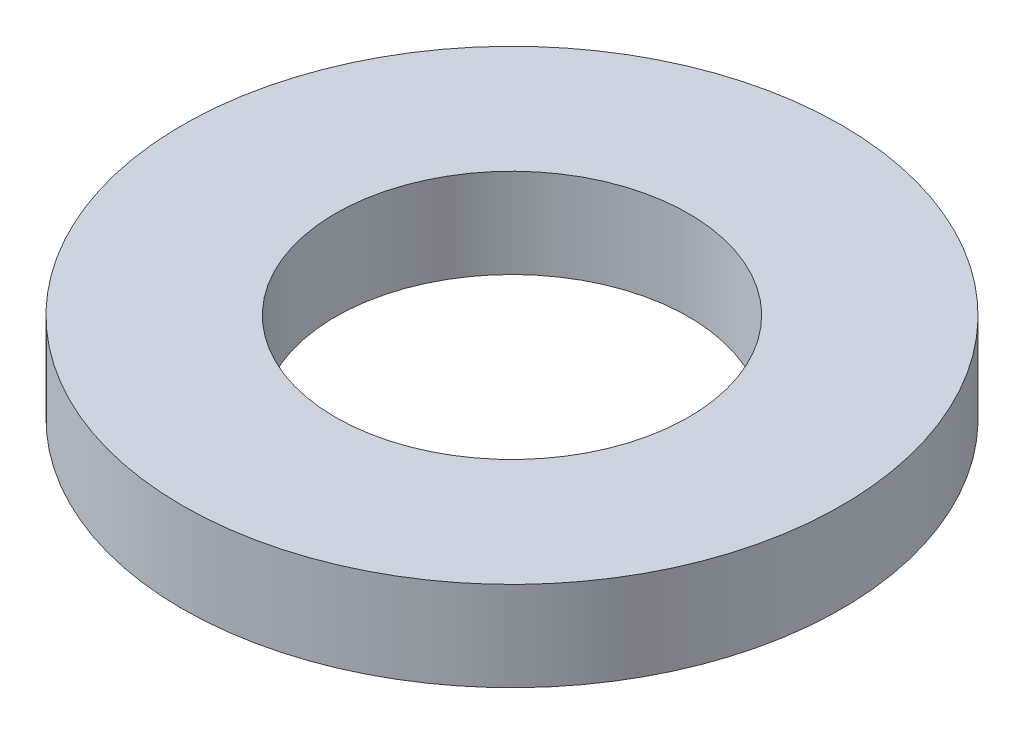
SolidWorks part; units mm, degrees
ref_plane "Front Plane" through (0, 0, 0) normal (0, 0, 1) x (1, 0, 0)
ref_plane "Top Plane" through (0, 0, 0) normal (0, 1, 0) x (1, 0, 0)
ref_plane "Right Plane" through (0, 0, 0) normal (1, 0, 0) x (0, 0, -1)
sketch "Sketch1" plane through (0, 0, 0) normal (0, 1, 0) x (1, 0, 0)
  circle A0 centre (0, 0) radius 70
  dimension "FLANGE_OD" = 140
extrude "Boss-Extrude1" add sketch "Sketch1" along normal blind 19
sketch "Sketch2" plane through (0, 0, 0) normal (0, 1, 0) x (1, 0, 0)
  circle A0 centre (0, 0) radius 37.5
  dimension "BORE_D" = 75
extrude "Cut-Extrude1" cut sketch "Sketch2" along normal through all
sketch "Sketch3" plane through (0, 19, 0) normal (0, 1, 0) x (1, 0, 0)
  circle A0 centre (0, 0) radius 30.9792 construction
  circle A1 centre (-30.9792, 0) radius 3.4929
  dimension "BOLT_D" = 6.9859
  dimension "BOLT_PCD" = 61.9583
extrude "Cut-Extrude2" cut sketch "Sketch3" against normal blind 18.9545 rebuild error yes
pattern_circular "CirPattern1" count 6 over 360 rebuild error yes
